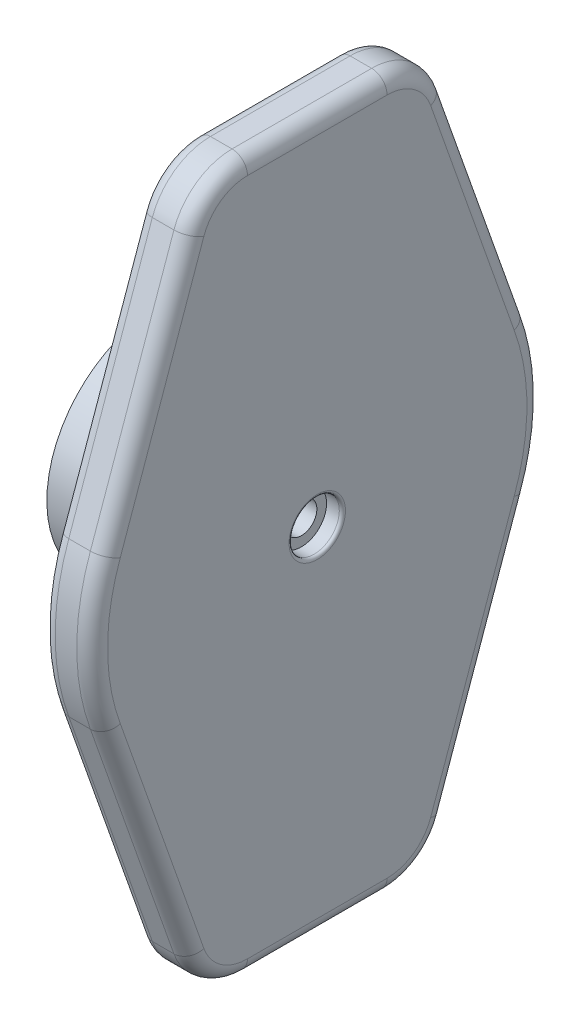
SolidWorks part; units mm, degrees
other "Markup1"
sketch "Sketch9" plane through (-25.745, 62.7203, -36.576) normal (-0.5706, 0.1284, -0.8112) x (-0.8147, 0.0363, 0.5788)
ref_plane "Front Plane" through (0, 0, 0) normal (0, 0, 1) x (1, 0, 0)
ref_plane "Top Plane" through (0, 0, 0) normal (0, 1, 0) x (1, 0, 0)
ref_plane "Right Plane" through (0, 0, 0) normal (1, 0, 0) x (0, 0, -1)
sketch "Sketch1" plane through (0, 0, 0) normal (0, 0, 1) x (1, 0, 0)
  line L0 (8.255, 0) -> (-8.255, 0) construction
  line L1 (25.855, 0) -> (-25.855, 0) construction
  line L2 (8.255, 0) -> (8.255, 18.25)
  line L3 (8.255, 18.25) -> (25.855, 18.25)
  line L4 (25.855, 18.25) -> (25.855, 0)
  line L5 (8.255, 0) -> (25.855, 0)
  point P4 (0, 0)
  point P8 (0, 0)
  dimension "D1" = 16.51
  dimension "D2" = 17.6
  dimension "D3" = 18.25
revolve "Revolve1" add sketch "Sketch1" angle 360 about L5
sketch "Sketch2" plane through (8.255, 0, 0) normal (-1, 0, 0) x (0, 0, 1)
  circle A0 centre (0, 0) radius 3.7145
  dimension "D1" = 7.429
extrude "Cut-Extrude1" cut sketch "Sketch2" against normal blind 8.5725
sketch "Sketch3" plane through (25.855, 0, 0) normal (1, 0, 0) x (0, 0, -1)
  line L5 (-20.7464, 50.832) -> (-34.2929, 12.5)
  line L6 (11.3179, -57.5) -> (-11.3179, -57.5)
  line L27 (11.3179, 57.5) -> (-11.3179, 57.5)
  line L38 (-34.2929, -12.5) -> (-20.7464, -50.832)
  line L39 (36.5, 0) -> (-36.5, 0) construction
  line L40 (0, -57.5) -> (0, 57.5) construction
  line L41 (34.2929, -12.5) -> (20.7464, -50.832)
  line L42 (20.7464, 50.832) -> (34.2929, 12.5)
  arc A3 (-34.2929, 12.5) -> (-34.2929, -12.5) centre (0, 0) ccw
  arc A4 (20.7464, -50.832) -> (11.3179, -57.5) centre (11.3179, -47.5) cw
  arc A5 (-11.3179, -57.5) -> (-20.7464, -50.832) centre (-11.3179, -47.5) cw
  arc A6 (11.3179, 57.5) -> (20.7464, 50.832) centre (11.3179, 47.5) cw
  arc A7 (-11.3179, 57.5) -> (-20.7464, 50.832) centre (-11.3179, 47.5) ccw
  arc A8 (34.2929, -12.5) -> (34.2929, 12.5) centre (0, 0) ccw
  point P16 (0, 0)
  point P20 (0, 0)
  circle M2 centre (0, 0) radius 18.25
  dimension "D3" = 115
  dimension "D5" = 22.6358
  dimension "D4" = 25
  dimension "D1" = 73
  dimension "D6" = 10
  dimension "D2" = 41.4929
  dimension "D8" = 22.6358
extrude "Boss-Extrude1" add sketch "Sketch3" along normal blind 8 separate body contours M2 | M2 region at (25.855, 54.5524, 16.3055) region at (25.855, 0, 0)
sketch "Sketch4" plane through (25.855, 0, 0) normal (-1, 0, 0) x (0, 0, 1)
  line L0 (-19.575, 55) -> (-6.775, 55) construction
  line L1 (13.175, -55) -> (-13.175, -55) construction
  line L2 (13.175, -55) -> (13.175, 55) construction
  line L3 (13.175, 55) -> (-13.175, 55) construction
  line L4 (-13.175, -55) -> (-13.175, 55) construction
  line L5 (13.175, -55) -> (-13.175, 55) construction
  line L6 (13.175, 55) -> (-13.175, -55) construction
  circle A0 centre (-13.175, 55) radius 4.75
  circle A1 centre (13.175, -55) radius 4.75
  circle A2 centre (13.175, 55) radius 4.75
  circle A3 centre (-13.175, -55) radius 4.75
  circle A5 centre (-13.175, 55) radius 6.4
  circle A6 centre (13.175, 55) radius 6.4
  circle A7 centre (13.175, -55) radius 6.4
  circle A8 centre (-13.175, -55) radius 6.4
  point P6 (0, 0)
  dimension "D1" = 9.5
  dimension "D2" = 12.8
  dimension "D3" = 26.35
  dimension "D4" = 110
sketch "Sketch5" plane through (8.255, 0, 0) normal (-1, 0, 0) x (0, 0, 1)
  circle A0 centre (0, 0) radius 18.25
  dimension "D1" = 36.5
sketch "Sketch6" plane through (8.255, 0, 0) normal (-1, 0, 0) x (0, 0, 1)
  circle A2 centre (0, 0) radius 13.125
  dimension "D1" = 26.25
extrude "Cut-Extrude2" cut sketch "Sketch6" against normal blind 17.8
ref_plane "Plane1" through (0, 0, 38) normal (0, 0, 1) x (1, 0, 0)
ref_plane "Plane2" through (24.855, 0, 0) normal (-1, 0, 0) x (0, 0, 1)
sketch "Sketch12" plane through (33.855, 0, 0) normal (1, 0, 0) x (0, 0, -1)
  circle A0 centre (0, 0) radius 4.075
  circle A1 centre (0, 0) radius 2.5
  dimension "D1" = 8.15
  dimension "D2" = 5
extrude "Cut-Extrude6" cut sketch "Sketch12" against normal blind 2.56 contours A0
extrude "Cut-Extrude7" cut sketch "Sketch12<6>" against normal through all contours A1 region at (33.855, 0, 0)
sketch "Sketch12<6>" plane through (33.855, 0, 0) normal (1, 0, 0) x (0, 0, -1) same geometry as "Sketch12"
fillet "Fillet2" radius 0.5 1 edges at (33.855, 4.075, 0)
combine bodies "Combine1" operation type add bodies to combine 124 127
fillet "Fillet3" radius 2 1 edges at (25.855, -18.25, 0)
sketch "Sketch13" plane through (0, 0, 0) normal (0, 0, 1) x (1, 0, 0)
  line L0 (8.255, 0) -> (23.855, 0) construction
  line L1 (8.255, 18.25) -> (8.255, -18.25) construction
  line L2 (23.855, 18.25) -> (23.855, -18.25) construction
  circle A0 centre (16.055, 0) radius 1.65
  dimension "D1" = 3.3
extrude "Cut-Extrude8" cut sketch "Sketch13" against normal mid plane 50
sketch "Sketch16" plane through (0, 0, 0) normal (0, 0, 1) x (1, 0, 0)
  circle A0 centre (16.055, 0) radius 3.2
  dimension "D1" = 6.4
extrude "Cut-Extrude11" cut sketch "Sketch16" against normal mid plane 31.5
fillet "Fillet4" radius 2.5 12 edges at (33.855, -55.6646, -17.092) (33.855, -57.5, 0) (33.855, -55.6646, 17.092) (33.855, -31.666, 27.5196) (33.855, 0, 36.5) (33.855, 31.666, 27.5196) (33.855, 55.6646, 17.092) (33.855, 57.5, 0) (33.855, 55.6646, -17.092) (33.855, 31.666, -27.5196) (33.855, 0, -36.5) (33.855, -31.666, -27.5196)
fillet "Fillet5" radius 2 12 edges at (25.855, 0, -36.5) (25.855, 31.666, -27.5196) (25.855, 55.6646, -17.092) (25.855, 57.5, 0) (25.855, 55.6646, 17.092) (25.855, 31.666, 27.5196) (25.855, 0, 36.5) (25.855, -31.666, 27.5196) (25.855, -55.6646, 17.092) (25.855, -57.5, 0) (25.855, -55.6646, -17.092) (25.855, -31.666, -27.5196)
